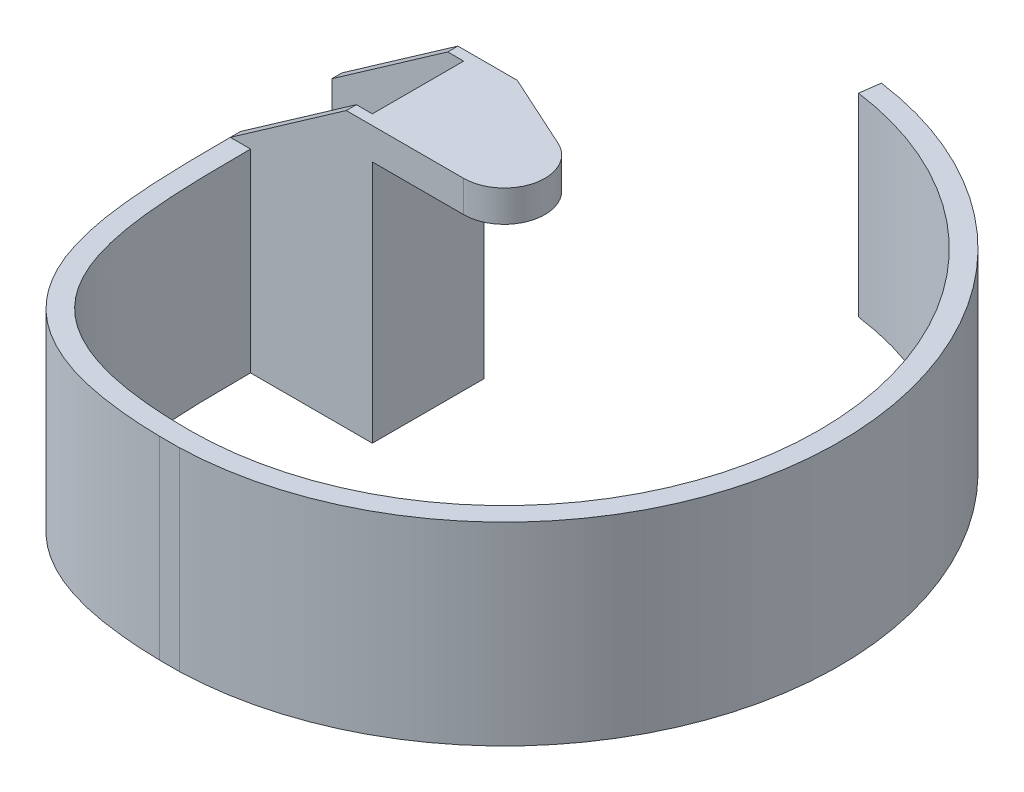
SolidWorks part; units mm, degrees
ref_plane "Front Plane" through (0, 0, 0) normal (0, 0, 1) x (1, 0, 0)
ref_plane "Top Plane" through (0, 0, 0) normal (0, 1, 0) x (1, 0, 0)
ref_plane "Right Plane" through (0, 0, 0) normal (1, 0, 0) x (0, 0, -1)
sketch "Agitator / Kick Alignment" plane through (0, 0, 0) normal (0, 1, 0) x (1, 0, 0)
  line L0 (-131.2224, 60.1613) -> (-110.3231, 213.6853) construction
  line L1 (5.6533, 41.527) -> (26.5533, 195.0509) construction
  line L2 (16.1033, 118.2889) -> (-271.78, 157.48) construction
  line L3 (-131.2224, 60.1613) -> (-110.3231, 213.6853)
  line L4 (5.6533, 41.527) -> (26.5533, 195.0509)
  line L5 (16.1033, 118.2889) -> (-271.78, 157.48)
sketch "Sketch3" plane through (0, 0, 0) normal (0, 1, 0) x (1, 0, 0)
  line L0 (5.6533, 41.527) -> (26.5533, 195.0509) construction
  line L1 (26.5533, 195.0509) -> (28.2664, 207.6348)
  line L2 (-133.35, -25.4) -> (0, -25.4)
  line L4 (-36.2865, 44.45) -> (-146.0084, 44.45)
  line L6 (-36.2865, 44.45) -> (10.5332, 23.113)
  line L7 (-6.3292, -209.4544) -> (6.3292, -209.4544)
  line L8 (128.5561, -196.85) -> (-132.7269, -196.85) construction
  line L9 (-146.0084, -25.4) -> (-146.0084, 44.45)
  line L10 (-133.35, -99.724) -> (-133.35, 83.6944) construction
  line L11 (-133.35, -25.4) -> (-133.35, 44.45)
  line L12 (-6.3292, -209.4544) -> (-6.3292, -209.4544)
  line L13 (-146.0084, -12.7416) -> (0, -12.7416) construction
  line L14 (-39.0349, 31.7916) -> (5.2839, 11.5944) construction
  line L15 (-39.0349, 31.7916) -> (-146.0084, 31.7916) construction
  line L16 (-133.35, -25.4) -> (-146.0084, -25.4)
  arc A0 (26.5533, 195.0509) -> (0, -196.85) centre (0, 0) cw
  arc A1 (28.2664, 207.6348) -> (6.3292, -209.4544) centre (0, 0) cw
  arc A4 (0, -25.4) -> (10.5332, 23.113) centre (0, 0) ccw
  arc A5 (0, -196.85) -> (-133.35, -25.4) centre (-91.3959, -130.3524) cw construction
  arc A6 (6.3292, -209.4544) -> (-138.0641, -13.6073) centre (-91.3959, -130.3524) cw construction
  arc A10 (-6.3292, -209.4544) -> (-6.3292, -209.4544) centre (-6.3292, -209.4544) cw
  arc A11 (-6.3292, -209.4544) -> (-6.3292, -209.4544) centre (-6.3292, -209.4544) ccw
  arc A12 (0, -12.7416) -> (5.2839, 11.5944) centre (0, 0) ccw construction
  spline S0 degree 1 poles (-146.0084, -12.7416) (-6.3292, -209.4544) knots 0 0 1 1 construction
  spline S1 degree 3 poles (-146.0084, -12.7416) (-146.0084, -14.4342) (-146.0083, -17.8078) (-146.0086, -21.6028) (-146.0083, -24.5474) (-146.0089, -27.9687) (-145.9928, -37.6758) (-145.8479, -52.8132) (-145.2521, -71.5713) (-144.0488, -89.4194) (-142.0319, -106.3622) (-137.955, -127.7287) (-131.2897, -147.2622) (-120.9286, -164.5766) (-111.1011, -176.2073) (-99.1376, -186.2307) (-85.0632, -194.4723) (-71.5911, -199.824) (-59.7326, -203.2181) (-50.2806, -205.3279) (-40.2501, -207.0086) (-31.3897, -208.0563) (-23.9871, -208.6846) (-18.276, -209.0513) (-13.3774, -209.2699) (-9.3819, -209.3926) (-7.3435, -209.4368) (-6.3292, -209.4544) knots -0.039869 -0.039869 -0.039869 -0.039869 -0.023876 -0.007997 -0.003998 0.003998 0.024105 0.088079 0.152052 0.216026 0.28 0.343974 0.471922 0.535895 0.599869 0.663843 0.727817 0.791791 0.823778 0.855765 0.887751 0.919738 0.935732 0.951725 0.967719 0.975715 0.983712 0.983712 0.983712 0.983712 only from (-146.0084, -25.4) to (-6.3292, -209.4544)
  spline S3 degree 3 poles (-133.35, -25.4) (-133.35, -131.2333) (-127, -196.85) (0, -196.85) knots 0 0 0 0 1 1 1 1
  point P22 (0, -209.4544)
  dimension "D1" = 196.85
  dimension "D6" = 25.4
  dimension "D9" = 317.5
  dimension "D10" = 381
  dimension "D3" = 12.7
  dimension "D4" = 69.85
  dimension "D7" = 24.5
  dimension "D8" = 133.35
extrude "Base extrude" add sketch "Sketch3" along normal blind 121.285 contours S3 L2 A4 L6 L4 L9 S1 L7 A1 L1 A0 region at (32.8405, 0, -200.6035)
extrude "Motor box & Core support" add sketch "Sketch3<4>" along normal offset from surface (172.085 mm away) 50.8 contours L16 L11 L4 L9 | L2 A4 L6 L4 L11 region at (-60.4233, 0, -7.6989) region at (-139.6792, 0, -9.525) up to face at (2.0047, 121.285, 15.5178) offset beyond the face yes
sketch "Sketch3<4>" plane through (0, 0, 0) normal (0, 1, 0) x (1, 0, 0) same geometry as "Sketch3"
sketch "Sketch4" plane through (0, 0, 25.4) normal (0, 0, 1) x (1, 0, 0)
  line L0 (25.4, 0) -> (25.4, 172.085) construction
  line L1 (25.4, 0) -> (-57.15, 0)
  line L2 (25.4, 0) -> (25.4, 152.4)
  line L3 (25.4, 152.4) -> (-57.15, 152.4)
  line L4 (-57.15, 0) -> (-57.15, 152.4)
  dimension "D1" = 152.4
  dimension "D2" = 82.55
extrude "Wheel space" cut sketch "Sketch4" against normal up to next
sketch "Sketch5" plane through (0, 172.085, 0) normal (0, 1, 0) x (1, 0, 0)
  line L0 (-146.0084, -25.4) -> (-146.0084, 44.45) construction
  line L7 (-63.5, 44.45) -> (-63.5, -25.4)
  line L8 (-63.5, 38.1) -> (-63.5, -19.05)
  line L18 (-146.0084, 38.1) -> (-146.0084, -19.05)
  line L22 (-139.6584, -19.05) -> (0, -19.05)
  line L23 (7.8999, 17.3348) -> (-37.6652, 38.1)
  line L24 (-37.6652, 38.1) -> (-139.6584, 38.1)
  line L25 (-139.6584, 38.1) -> (-139.6584, -19.05)
  line L26 (-146.0084, -19.05) -> (-63.5, -19.05)
  line L28 (-63.5, 38.1) -> (-146.0084, 38.1)
  arc A4 (0, -19.05) -> (7.8999, 17.3348) centre (0, 0) ccw
  point P0 (0, 0)
  point P4 (0, 0)
  point P5 (0, 0)
  dimension "D1" = 6.35
  dimension "D2" = 6.35
extrude "Motor space" cut sketch "Sketch5" against normal offset from surface (121.285 mm away) 50.8 up to face at (-24.6276, 0, 4.5125)
sketch "Sketch6" plane through (0, 0, 25.4) normal (0, 0, 1) x (1, 0, 0)
  line L0 (-146.0084, 121.285) -> (-73.4585, 172.085)
  line L1 (0, 172.085) -> (-146.0084, 172.085) construction
  line L2 (-73.4585, 172.085) -> (-146.0084, 172.085)
  line L3 (-146.0084, 172.085) -> (-146.0084, 121.285)
  dimension "D1" = 35
extrude "Motor Space Ribs" cut sketch "Sketch6" against normal through all
